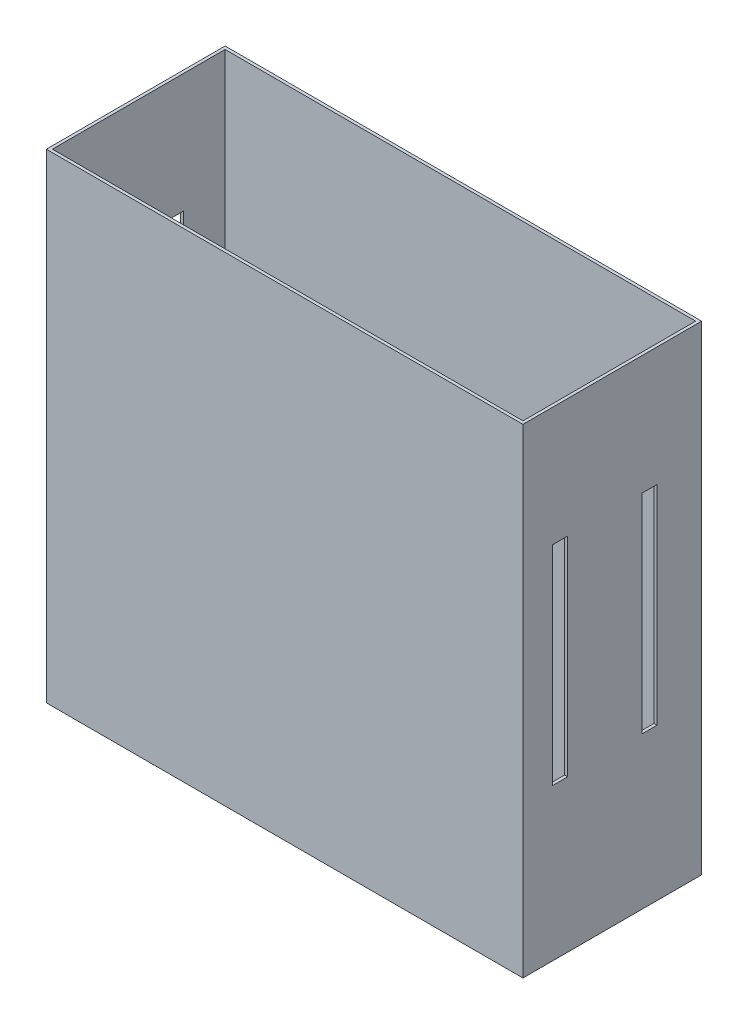
SolidWorks part; units mm, degrees
ref_plane "Front Plane" through (0, 0, 0) normal (0, 0, 1) x (1, 0, 0)
ref_plane "Top Plane" through (0, 0, 0) normal (0, 1, 0) x (1, 0, 0)
ref_plane "Right Plane" through (0, 0, 0) normal (1, 0, 0) x (0, 0, -1)
sketch "Sketch1" plane through (0, 0, 0) normal (0, 1, 0) x (1, 0, 0)
  line L0 (-200.66, 73.66) -> (200.66, 73.66)
  line L1 (-203.2, 76.2) -> (203.2, 76.2)
  line L2 (-203.2, 76.2) -> (-203.2, -76.2)
  line L3 (-203.2, -76.2) -> (203.2, -76.2)
  line L4 (203.2, 76.2) -> (203.2, -76.2)
  line L5 (-203.2, 76.2) -> (203.2, -76.2) construction
  line L6 (-203.2, -76.2) -> (203.2, 76.2) construction
  line L7 (200.66, 73.66) -> (200.66, -73.66)
  line L8 (-200.66, -73.66) -> (200.66, -73.66)
  line L9 (-200.66, 73.66) -> (-200.66, -73.66)
  point P4 (0, 0)
  dimension "D1" = 406.4
  dimension "D2" = 152.4
  dimension "D3" = 2.54
extrude "Boss-Extrude1" add sketch "Sketch1" along normal blind 406.4
sketch "Sketch2" plane through (0, 0, 0) normal (0, -1, 0) x (1, 0, 0)
  line L0 (203.2, 76.2) -> (203.2, -76.2) construction
  line L1 (-203.2, -76.2) -> (-203.2, 76.2) construction
  line L2 (-203.2, 76.2) -> (203.2, 76.2) construction
  line L3 (203.2, -76.2) -> (-203.2, -76.2) construction
  line L4 (203.2, 76.2) -> (203.2, -76.2)
  line L5 (-203.2, -76.2) -> (-203.2, 76.2)
  line L6 (-203.2, 76.2) -> (203.2, 76.2)
  line L7 (203.2, -76.2) -> (-203.2, -76.2)
extrude "Boss-Extrude2" add sketch "Sketch2" along normal blind 2.54
sketch "Sketch3" plane through (-203.2, 0, 0) normal (-1, 0, 0) x (0, 0, 1)
  line L0 (76.2, 406.4) -> (76.2, -2.54) construction
  line L1 (38.1, 304.8) -> (50.8, 304.8)
  line L2 (38.1, 304.8) -> (38.1, 127)
  line L3 (38.1, 127) -> (50.8, 127)
  line L4 (50.8, 304.8) -> (50.8, 127)
  line L5 (38.1, 304.8) -> (50.8, 127) construction
  line L6 (38.1, 127) -> (50.8, 304.8) construction
  line L7 (76.2, -2.54) -> (-76.2, -2.54) construction
  line L8 (38.1, 304.8) -> (-25.4, 304.8) construction
  line L9 (38.1, 127) -> (-25.4, 127) construction
  line L11 (-25.4, 127) -> (-38.1, 127)
  line L12 (-25.4, 127) -> (-25.4, 304.8)
  line L13 (-25.4, 304.8) -> (-38.1, 304.8)
  line L14 (-38.1, 127) -> (-38.1, 304.8)
  line L15 (-25.4, 127) -> (-38.1, 304.8) construction
  line L16 (-25.4, 304.8) -> (-38.1, 127) construction
  point P4 (44.45, 215.9)
  point P14 (-31.75, 215.9)
  dimension "D1" = 12.7
  dimension "D2" = 177.8
  dimension "D3" = 25.4
  dimension "D4" = 129.54
  dimension "D5" = 12.7
  dimension "D6" = 63.5
extrude "Cut-Extrude1" cut sketch "Sketch3" against normal through all both and the other way through all
